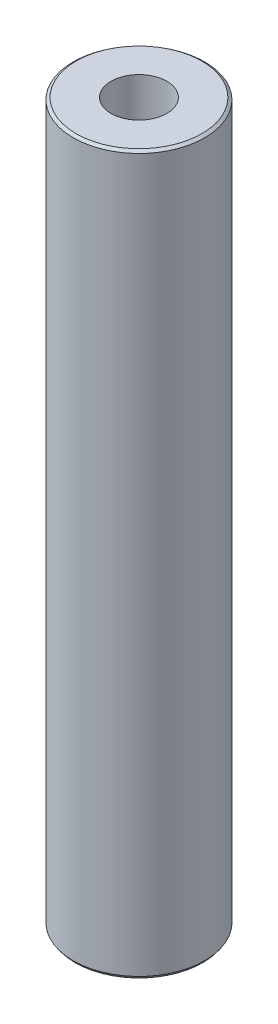
SolidWorks part; units mm, degrees
ref_plane "Front Plane" through (0, 0, 0) normal (0, 0, 1) x (1, 0, 0)
ref_plane "Top Plane" through (0, 0, 0) normal (0, 1, 0) x (1, 0, 0)
ref_plane "Right Plane" through (0, 0, 0) normal (1, 0, 0) x (0, 0, -1)
sketch "Sketch1" plane through (0, 0, 0) normal (0, 1, 0) x (1, 0, 0)
  circle A0 centre (0, 0) radius 55
  dimension "SHAFT_OD" = 110
extrude "Boss-Extrude1" add sketch "Sketch1" along normal blind 600
sketch "Sketch2" plane through (0, 0, 0) normal (0, 1, 0) x (1, 0, 0)
  circle A0 centre (0, 0) radius 23.3329
  dimension "BORE_D" = 46.6659
extrude "Cut-Extrude1" cut sketch "Sketch2" along normal through all
chamfer "Chamfer1" distance 1.7611 angle 53.755 2 edges at (0, 600, 55) (0, 0, 55) first distance on face at (0, 600, 55) first distance on face at (0, 0, 23.3329)
